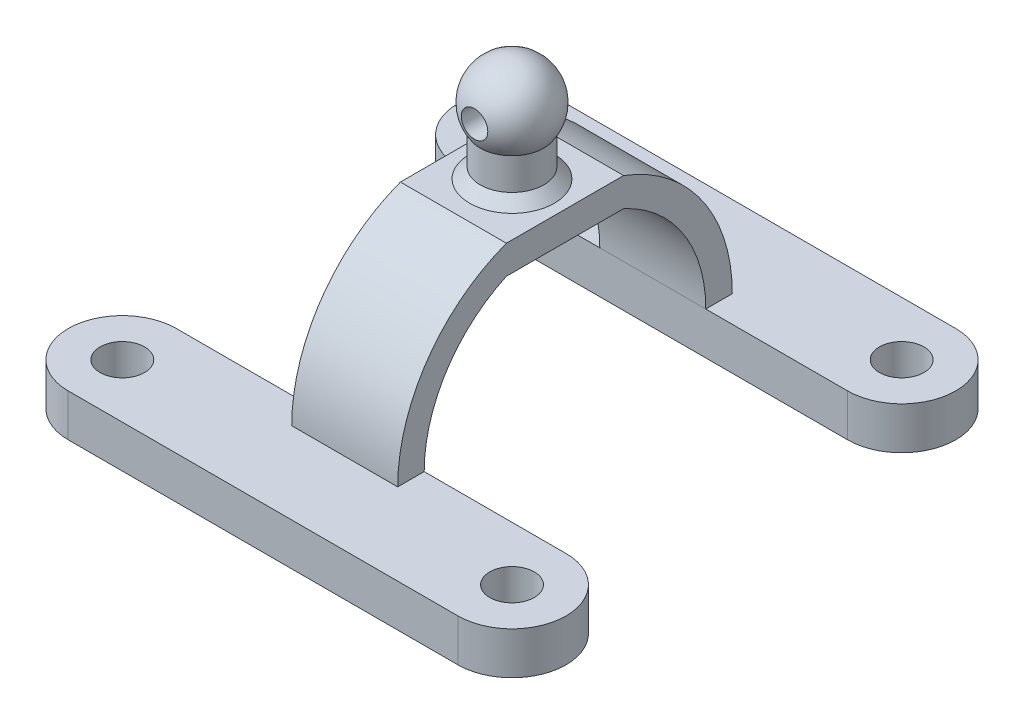
SolidWorks part; units mm, degrees
ref_plane "正面" through (0, 0, 0) normal (0, 0, 1) x (1, 0, 0)
ref_plane "平面" through (0, 0, 0) normal (0, 1, 0) x (1, 0, 0)
ref_plane "右側面" through (0, 0, 0) normal (1, 0, 0) x (0, 0, -1)
sketch "ｽｹｯﾁ1" plane through (0, 16.995, 0) normal (0, 1, 0) x (1, 0, 0)
  circle A0 centre (0, 0) radius 26.0003 construction
  circle A24 centre (-18.385, 18.385) radius 2.1
  circle A25 centre (-18.385, -18.385) radius 2.1
  circle A26 centre (18.385, -18.385) radius 2.1
  circle A27 centre (18.385, 18.385) radius 2.1
  circle A28 centre (-18.385, 18.385) radius 3.6
  circle A29 centre (18.385, 18.385) radius 3.6
  circle A30 centre (18.385, -18.385) radius 3.6
  circle A31 centre (-18.385, -18.385) radius 3.6
  dimension "D1" = 4.2
  dimension "D2" = 4.2
  dimension "D3" = 4.2
  dimension "D4" = 4.2
  dimension "D6" = 36.77
  dimension "D7" = 36.77
  dimension "D5" = 1.5
extrude "ﾎﾞｽ - 押し出し1" add sketch "ｽｹｯﾁ1" along normal blind 1
sketch "ｽｹｯﾁ2" plane through (0, 17.995, 0) normal (0, 1, 0) x (1, 0, 0)
  circle A0 centre (-18.385, 18.385) radius 3.6 construction
  circle A1 centre (-18.385, -18.385) radius 3.6 construction
  circle A2 centre (18.385, -18.385) radius 3.6 construction
  circle A3 centre (18.385, 18.385) radius 3.6 construction
  circle A4 centre (-18.385, 18.385) radius 3.6
  circle A5 centre (-18.385, -18.385) radius 3.6
  circle A6 centre (18.385, -18.385) radius 3.6
  circle A7 centre (18.385, 18.385) radius 3.6
  circle A8 centre (18.385, 18.385) radius 3.6
  circle A9 centre (18.385, -18.385) radius 2.1
  circle A10 centre (18.385, -18.385) radius 2.1
  circle A11 centre (-18.385, -18.385) radius 2.1
  circle A12 centre (-18.385, -18.385) radius 2.1
  circle A13 centre (-18.385, 18.385) radius 2.1
  circle A14 centre (-18.385, 18.385) radius 2.1
  circle A15 centre (18.385, 18.385) radius 2.1
  circle A16 centre (18.385, 18.385) radius 2.1
  circle A17 centre (18.385, -18.385) radius 3.6
  circle A18 centre (-18.385, -18.385) radius 3.6
  circle A19 centre (-18.385, 18.385) radius 3.6
  circle A20 centre (-18.385, 18.385) radius 5.1
  circle A21 centre (18.385, 18.385) radius 5.1
  circle A22 centre (18.385, -18.385) radius 5.1
  circle A23 centre (-18.385, -18.385) radius 5.1
  circle M6 centre (18.385, -18.385) radius 3.6
  circle M7 centre (18.385, -18.385) radius 2.1
  dimension "D1" = 0
  dimension "D2" = 0
  dimension "D3" = 0
  dimension "D4" = 0
  dimension "D5" = 1.5
extrude "ﾎﾞｽ - 押し出し2" add sketch "ｽｹｯﾁ2" along normal blind 4 contours A4 A14 | A20 A4 | A7 A16 | A21 A7 | M6 M7 | A22 M6 | A5 A12 | A23 A5 region at (-21.8832, 17.995, -18.385) region at (-21.8832, 17.995, 18.385) region at (14.8868, 17.995, 18.385) region at (14.8868, 17.995, -18.385) region at (-23.3408, 17.995, -18.385) region at (13.4292, 17.995, -18.385) region at (13.4292, 17.995, 18.385) region at (-23.3408, 17.995, 18.385)
sketch "ｽｹｯﾁ3" plane through (0, 21.995, 0) normal (0, 1, 0) x (1, 0, 0)
  line L0 (-18.385, 13.285) -> (18.385, 13.285)
  line L5 (-18.385, 23.485) -> (18.385, 23.485)
  line L6 (-18.385, 23.485) -> (-18.385, 13.285)
  line L11 (-18.385, -23.485) -> (18.385, -23.485)
  line L12 (18.385, 23.485) -> (18.385, 13.285)
  line L13 (-18.385, -13.285) -> (18.385, -13.285)
  line L14 (-18.385, -13.285) -> (-18.385, -23.485)
  line L15 (18.385, -13.285) -> (18.385, -23.485)
  circle A8 centre (-18.385, -18.385) radius 5.1 construction
  circle A9 centre (18.385, -18.385) radius 5.1 construction
  circle A10 centre (18.385, 18.385) radius 5.1 construction
  circle A11 centre (-18.385, 18.385) radius 5.1 construction
  circle A12 centre (-18.385, -18.385) radius 5.1
  circle A13 centre (18.385, -18.385) radius 5.1
  circle A14 centre (18.385, 18.385) radius 5.1
  circle A15 centre (-18.385, 18.385) radius 5.1
  circle A16 centre (-18.385, 18.385) radius 2.1 construction
  circle A17 centre (-18.385, -18.385) radius 2.1 construction
  circle A18 centre (18.385, -18.385) radius 2.1 construction
  circle A19 centre (18.385, 18.385) radius 2.1 construction
  circle A20 centre (-18.385, 18.385) radius 2.1
  circle A21 centre (-18.385, -18.385) radius 2.1
  circle A22 centre (18.385, -18.385) radius 2.1
  circle A23 centre (18.385, 18.385) radius 2.1
  circle M3 centre (18.385, -18.385) radius 5.1
extrude "ﾎﾞｽ - 押し出し3" add sketch "ｽｹｯﾁ3" against normal blind 4 contours A20 | M3 | A15 L0 A14 L5 region at (0, 21.995, -18.385) region at (-15.9605, 21.995, -18.385) region at (0, 21.995, 18.385)
sketch "ｽｹｯﾁ4" plane through (0, 0, 0) normal (1, 0, 0) x (0, 0, -1)
  line L0 (13.285, 17.995) -> (23.485, 17.995) construction
  line L2 (23.485, 21.995) -> (13.285, 21.995) construction
  line L5 (-13.285, 21.995) -> (-23.485, 21.995) construction
  line L7 (-23.485, 17.995) -> (-13.285, 17.995) construction
  line L8 (13.285, 17.995) -> (23.485, 17.995)
  line L10 (23.485, 21.995) -> (13.285, 21.995)
  line L13 (-13.285, 21.995) -> (-23.485, 21.995)
  line L15 (-23.485, 17.995) -> (-13.285, 17.995)
  line L16 (-13.285, 17.995) -> (-13.285, 21.995) construction
  line L17 (0, 21.995) -> (0, 37.78) construction
  line L18 (-23.485, 17.995) -> (-23.485, 21.995) construction
  line L19 (-5.529, 36.78) -> (5.529, 36.78)
  line L20 (-5.529, 36.78) -> (-5.529, 34.0748)
  line L21 (-5.529, 34.0748) -> (5.529, 34.0748)
  line L22 (5.529, 36.78) -> (5.529, 34.0748)
  line L23 (-13.285, 17.995) -> (-13.285, 21.995)
  line L24 (-23.485, 17.995) -> (-23.485, 21.995)
  line L25 (23.485, 17.995) -> (23.485, 21.995) construction
  line L26 (13.285, 17.995) -> (13.285, 21.995) construction
  line L27 (23.485, 17.995) -> (23.485, 21.995)
  line L28 (13.285, 17.995) -> (13.285, 21.995)
  arc A0 (-13.285, 21.995) -> (13.285, 21.995) centre (0, 21.995) cw
  arc A1 (-15.785, 21.995) -> (15.785, 21.995) centre (0, 21.995) cw
  dimension "D1" = 2.5
  dimension "D2" = 1
extrude "ﾎﾞｽ - 押し出し4" add sketch "ｽｹｯﾁ4" along normal mid plane 10 contours A1 L13 A0 L20 | L21 L17 A0 | A0 L17 L19 L20 | L17 A0 L22 L19 | L17 L21 A0 | A1 L22 A0 L10 region at (0, 29.6544, -11.4171) region at (0, 35.7993, -3.0548) region at (0, 34.5588, -2.0865) region at (0, 34.5588, 2.0865) region at (0, 35.7993, 3.0548) region at (0, 29.6544, 11.4171)
sketch "ｽｹｯﾁ5" plane through (0, 36.78, 0) normal (0, 1, 0) x (1, 0, 0)
  circle A0 centre (0, 0) radius 4
  dimension "D1" = 8
extrude "ﾎﾞｽ - 押し出し5" add sketch "ｽｹｯﾁ5" along normal blind 1
sketch "ｽｹｯﾁ6" plane through (0, 37.78, 0) normal (0, 1, 0) x (1, 0, 0)
  circle A0 centre (0, 0) radius 3
  dimension "D1" = 6
extrude "ﾎﾞｽ - 押し出し6" add sketch "ｽｹｯﾁ6" along normal blind 3
sketch "ｽｹｯﾁ7" plane through (0, 0, 0) normal (0, 0, 1) x (1, 0, 0)
  line L0 (3, 40.78) -> (-3, 40.78) construction
  line L1 (3, 40.78) -> (-3, 40.78)
  line L2 (0, 40.78) -> (0, 45.78) construction
  line L3 (0, 40.78) -> (0, 46.78)
  circle A0 centre (0, 43.03) radius 3.75
  dimension "D1" = 5
  dimension "D2" = 7.5
revolve "回転2" add sketch "ｽｹｯﾁ7" angle 360 about L2 region at (1.6628, 43.5051, 0)
sketch "ｽｹｯﾁ8" plane through (0, 0, 0) normal (0, 0, 1) x (1, 0, 0)
  arc A0 (3, 40.78) -> (-3, 40.78) centre (0, 43.03) ccw construction
  arc A1 (3, 40.78) -> (-3, 40.78) centre (0, 43.03) ccw
  circle A2 centre (0, 43.03) radius 1.25
  dimension "D2" = 2.5
extrude "ｶｯﾄ - 押し出し1" cut sketch "ｽｹｯﾁ8" against normal mid plane 12.5 contours A2 region at (0, 43.03, 0)
chamfer "面取り1" distance 1 angle 45 1 edges at (0, 37.78, 4)
